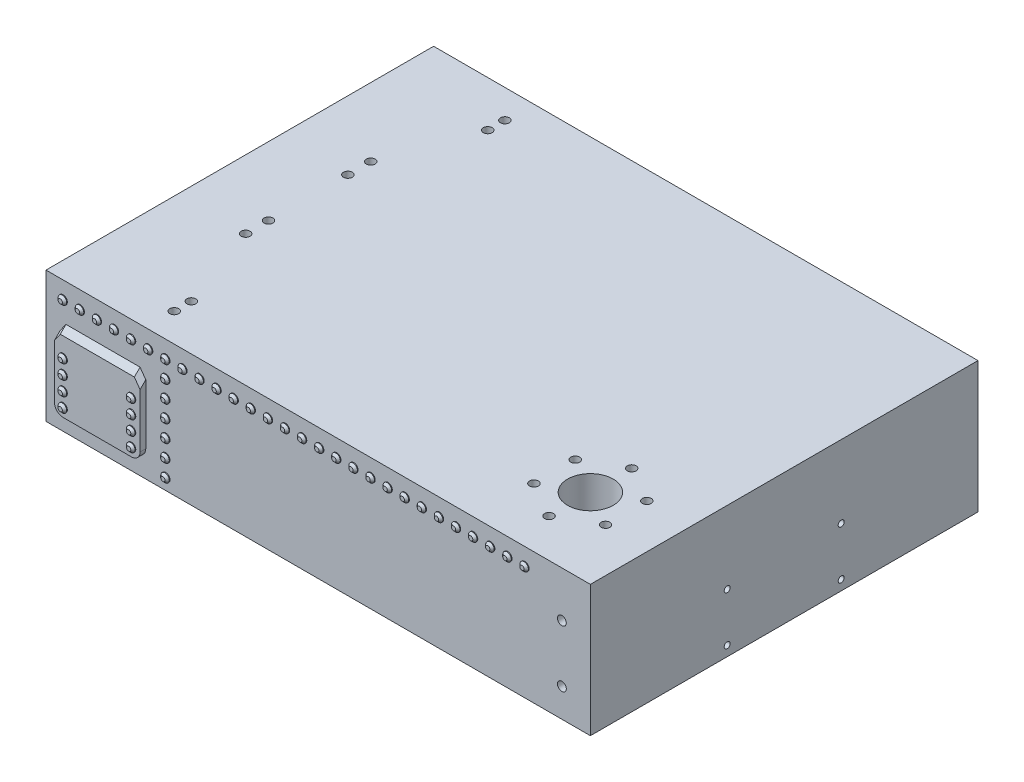
SolidWorks part; units mm, degrees
ref_plane "Front Plane" through (0, 0, 0) normal (0, 0, 1) x (1, 0, 0)
ref_plane "Top Plane" through (0, 0, 0) normal (0, 1, 0) x (1, 0, 0)
ref_plane "Right Plane" through (0, 0, 0) normal (1, 0, 0) x (0, 0, -1)
sketch "Sketch1" plane through (0, 0, 0) normal (0, 1, 0) x (1, 0, 0)
  line L1 (0, 0) -> (191, 0)
  line L2 (0, 0) -> (0, 136)
  line L3 (0, 136) -> (191, 136)
  line L4 (191, 0) -> (191, 136)
  dimension "D1" = 191
  dimension "D2" = 136
extrude "Boss-Extrude1" add sketch "Sketch1" along normal blind 46
sketch "Sketch3" plane through (0, 0, 0) normal (0, -1, 0) x (1, 0, 0)
  line L0 (0, -136) -> (0, 0) construction
  line L1 (5, -5) -> (186, -5)
  line L2 (5, -5) -> (5, -131)
  line L3 (5, -131) -> (186, -131)
  line L4 (186, -5) -> (186, -131)
  line L6 (191, -136) -> (0, -136) construction
  line L7 (191, 0) -> (191, -136) construction
  line L8 (0, 0) -> (191, 0) construction
  dimension "D1" = 5
  dimension "D2" = 5
  dimension "D3" = 5
  dimension "D4" = 5
extrude "Cut-Extrude1" cut sketch "Sketch3" against normal offset from surface (41 mm away) 5 contours L2 L3 L4 L1 up to face at (95.5, 46, -68)
ref_point "FrontLeft"
sketch "Sketch5" plane through (0, 0, -136) normal (0, 0, -1) x (-1, 0, 0)
  line L0 (-191, 46) -> (-119.5, 46)
  line L1 (-191, 46) -> (0, 46) construction
  line L2 (-119.5, 46) -> (-119.5, 0) construction
  line L3 (-191, 0) -> (0, 0) construction
  point P5 (-119.5, 23)
  dimension "D1" = 71.5
sketch "Sketch8" plane through (0, 0, 0) normal (0, 0, 1) x (1, 0, 0)
  line L1 (119.5, 46) -> (119.5, 0) construction
  line L2 (0, 46) -> (191, 46) construction
  line L3 (0, 0) -> (191, 0) construction
  point P0 (119.5, 23)
ref_point "SuspensionMountLeft"
ref_point "SuspensionMountRight"
sketch "Sketch9" plane through (0, 0, -136) normal (0, 0, -1) x (-1, 0, 0)
  line L0 (0, 46) -> (0, 0) construction
  line L1 (-5, 31) -> (-35, 31)
  line L2 (-5, 31) -> (-5, 6.2153)
  line L3 (-5, 6.2153) -> (-35, 6.2153)
  line L4 (-35, 31) -> (-35, 6.2153)
  line L5 (-191, 46) -> (0, 46) construction
  dimension "D1" = 5
  dimension "D2" = 15
  dimension "D3" = 30
extrude "Boss-Extrude2" add sketch "Sketch9" along normal blind 2
chamfer "Chamfer2" distance 2 angle 45 1 edges at (20, 31, -136)
fillet "Fillet1" radius 3 2 edges at (35, 6.2153, -137) (5, 6.2153, -137)
chamfer "Chamfer3" distance 2 angle 45 2 edges at (35, 32, -137) (5, 32, -137)
sketch "Sketch10" plane through (0, 0, 0) normal (0, 0, 1) x (1, 0, 0)
  line L4 (35, 31) -> (5, 31)
  line L5 (35, 6.2153) -> (35, 31)
  line L6 (5, 6.2153) -> (35, 6.2153)
  line L7 (5, 31) -> (5, 6.2153)
  line L8 (35, 31) -> (5, 31)
  line L9 (35, 6.2153) -> (35, 31)
  line L10 (5, 6.2153) -> (35, 6.2153)
  line L11 (5, 31) -> (5, 6.2153)
  dimension "D1" = 0
extrude "Boss-Extrude3" add sketch "Sketch10" along normal blind 2
chamfer "Chamfer4" distance 2 angle 45 1 edges at (20, 31, 0)
fillet "Fillet2" radius 3 2 edges at (35, 6.2153, 1) (5, 6.2153, 1)
chamfer "Chamfer5" distance 2 angle 45 2 edges at (35, 32, 1) (5, 32, 1)
sketch "Sketch23" plane through (0, 0, 2) normal (0, 0, 1) x (1, 0, 0)
  line L0 (8, 9.2153) -> (8, 31) construction
  line L1 (33, 31) -> (7, 31) construction
  line L2 (32, 9.2153) -> (32, 31) construction
  circle A0 centre (8, 9.2153) radius 1.5
  circle A1 centre (32, 9.2153) radius 1.5
  circle A2 centre (8, 14.2153) radius 1.5
  circle A3 centre (32, 14.2153) radius 1.5
  circle A4 centre (8, 19.2153) radius 1.5
  circle A5 centre (32, 19.2153) radius 1.5
  circle A6 centre (8, 24.2153) radius 1.5
  circle A7 centre (32, 24.2153) radius 1.5
  dimension "D1" = 3
  dimension "D2" = 3
  dimension "D3" = 4
extrude "Boss-Extrude8" add sketch "Sketch23" along normal blind 1 contours A4 | A2 | A0 | A1 | A3 | A5 | A7 | A6 region at (8, 9.2153, 2) region at (32, 9.2153, 2) region at (8, 14.2153, 2) region at (32, 14.2153, 2) region at (8, 19.2153, 2) region at (32, 19.2153, 2) region at (32, 24.2153, 2)
chamfer "Chamfer11" distance 0.75 angle 45 8 edges at (9.5, 24.2153, 3) (33.5, 9.2153, 3) (33.5, 14.2153, 3) (33.5, 19.2153, 3) (33.5, 24.2153, 3) (9.5, 9.2153, 3) (9.5, 14.2153, 3) (9.5, 19.2153, 3)
ref_plane "Plane1" through (0, 0, -68) normal (0, 0, 1) x (1, 0, 0)
mirror "Mirror1" about plane through (0, 0, -68) normal (0, 0, 1) of "Chamfer11", "Boss-Extrude8"
sketch "Sketch18" plane through (0, 41, 0) normal (0, -1, 0) x (1, 0, 0)
  line L25 (77.9594, -66) -> (76.1297, -62.8309)
  line L26 (76.1297, -62.8309) -> (72.4703, -62.8309)
  line L27 (72.4703, -62.8309) -> (70.6406, -66)
  line L28 (70.6406, -66) -> (72.4703, -69.1691)
  line L29 (72.4703, -69.1691) -> (76.1297, -69.1691)
  line L30 (76.1297, -69.1691) -> (77.9594, -66)
  line L31 (178.5415, -60.5) -> (176.5207, -57)
  line L32 (176.5207, -57) -> (172.4793, -57)
  line L33 (172.4793, -57) -> (170.4585, -60.5)
  line L34 (170.4585, -60.5) -> (172.4793, -64)
  line L35 (172.4793, -64) -> (176.5207, -64)
  line L36 (176.5207, -64) -> (178.5415, -60.5)
  line L37 (78.3415, -114) -> (76.3207, -110.5)
  line L38 (76.3207, -110.5) -> (72.2793, -110.5)
  line L39 (72.2793, -110.5) -> (70.2585, -114)
  line L40 (70.2585, -114) -> (72.2793, -117.5)
  line L41 (72.2793, -117.5) -> (76.3207, -117.5)
  line L42 (76.3207, -117.5) -> (78.3415, -114)
  line L43 (178.5415, -113) -> (176.5207, -109.5)
  line L44 (176.5207, -109.5) -> (172.4793, -109.5)
  line L45 (172.4793, -109.5) -> (170.4585, -113)
  line L46 (170.4585, -113) -> (172.4793, -116.5)
  line L47 (172.4793, -116.5) -> (176.5207, -116.5)
  line L48 (176.5207, -116.5) -> (178.5415, -113)
  circle A1 centre (74.3, -66) radius 3.1691 construction
  circle A2 centre (174.5, -60.5) radius 1.5
  circle A3 centre (174.5, -60.5) radius 1.5
  circle A4 centre (174.5, -113) radius 1.5
  circle A5 centre (174.5, -113) radius 1.5
  circle A6 centre (74.3, -114) radius 1.5
  circle A7 centre (74.3, -114) radius 1.5
  circle A8 centre (74.3, -66) radius 1.5
  circle A12 centre (74.3, -66) radius 1.5
  circle A13 centre (174.5, -60.5) radius 3.5 construction
  circle A14 centre (74.3, -114) radius 3.5 construction
  circle A15 centre (174.5, -113) radius 3.5 construction
  dimension "D1" = 0
  dimension "D2" = 0
  dimension "D3" = 0
  dimension "D4" = 0
extrude "Boss-Extrude7" add sketch "Sketch18" along normal blind 14 contours L29 L30 L25 L26 L27 L28 A12 | A12 | L41 L42 L37 L38 L39 L40 A7 | A7 | L47 L48 L43 L44 L45 L46 A5 | A5 | L35 L36 L31 L32 L33 L34 A3 | A3 region at (76.9607, 41, -67.5361) region at (177.4385, 41, -62.1965) region at (77.2385, 41, -115.6965) region at (177.4385, 41, -114.6965) region at (174.5, 41, -60.5) region at (174.5, 41, -113) region at (74.3, 41, -114) region at (74.3, 41, -66)
sketch "Sketch22" plane through (0, 0, 0) normal (-1, 0, 0) x (0, 0, 1)
  line L0 (0, 46) -> (0, 0) construction
  line L1 (-10, 10) -> (-80, 10)
  line L2 (-10, 10) -> (-10, 38)
  line L3 (-10, 38) -> (-80, 38)
  line L4 (-80, 10) -> (-80, 38)
  line L5 (-136, 0) -> (0, 0) construction
  line L6 (-136, 46) -> (0, 46) construction
  dimension "D1" = 10
  dimension "D2" = 10
  dimension "D3" = 8
  dimension "D4" = 70
extrude "Cut-Extrude2" [suppressed] cut sketch "Sketch22" against normal up to next
chamfer "Chamfer10" [suppressed] distance 28 angle 45
fillet "Fillet3" [suppressed] radius 3
sketch "Sketch24" plane through (0, 0, 0) normal (0, 0, 1) x (1, 0, 0)
  line L0 (0, 40) -> (191, 40) construction
  line L1 (0, 46) -> (0, 0) construction
  line L2 (191, 46) -> (191, 0) construction
  line L3 (0, 46) -> (191, 46) construction
  circle A0 centre (6, 40) radius 1.5
  circle A1 centre (12, 40) radius 1.5
  circle A2 centre (18, 40) radius 1.5
  circle A3 centre (24, 40) radius 1.5
  circle A4 centre (30, 40) radius 1.5
  circle A5 centre (36, 40) radius 1.5
  circle A6 centre (42, 40) radius 1.5
  circle A7 centre (48, 40) radius 1.5
  circle A8 centre (54, 40) radius 1.5
  circle A9 centre (60, 40) radius 1.5
  circle A10 centre (66, 40) radius 1.5
  circle A11 centre (72, 40) radius 1.5
  circle A12 centre (78, 40) radius 1.5
  circle A13 centre (84, 40) radius 1.5
  circle A14 centre (90, 40) radius 1.5
  circle A15 centre (96, 40) radius 1.5
  circle A16 centre (102, 40) radius 1.5
  circle A17 centre (108, 40) radius 1.5
  circle A18 centre (114, 40) radius 1.5
  circle A19 centre (120, 40) radius 1.5
  circle A20 centre (126, 40) radius 1.5
  circle A21 centre (132, 40) radius 1.5
  circle A22 centre (138, 40) radius 1.5
  circle A23 centre (144, 40) radius 1.5
  circle A24 centre (150, 40) radius 1.5
  circle A25 centre (156, 40) radius 1.5
  circle A26 centre (162, 40) radius 1.5
  circle A27 centre (168, 40) radius 1.5
  circle A28 centre (42, 34) radius 1.5
  circle A29 centre (42, 28) radius 1.5
  circle A30 centre (42, 22) radius 1.5
  circle A31 centre (42, 16) radius 1.5
  circle A32 centre (42, 10) radius 1.5
  circle A33 centre (42, 4) radius 1.5
  dimension "D2" = 3
  dimension "D1" = 6
  dimension "D3" = 6
  dimension "D4" = 28
  dimension "D5" = 7
extrude "Boss-Extrude9" add sketch "Sketch24" along normal blind 1
chamfer "Chamfer12" distance 0.75 angle 45 34 edges at (169.5, 40, 1) (163.5, 40, 1) (157.5, 40, 1) (151.5, 40, 1) (145.5, 40, 1) (139.5, 40, 1) (133.5, 40, 1) (127.5, 40, 1) (121.5, 40, 1) (115.5, 40, 1) (109.5, 40, 1) (103.5, 40, 1) (97.5, 40, 1) (91.5, 40, 1) (85.5, 40, 1) (79.5, 40, 1) (73.5, 40, 1) (67.5, 40, 1) (43.5, 4, 1) (43.5, 10, 1) (43.5, 16, 1) (43.5, 22, 1) (43.5, 28, 1) (43.5, 34, 1) (61.5, 40, 1) (55.5, 40, 1) (49.5, 40, 1) (43.5, 40, 1) (37.5, 40, 1) (31.5, 40, 1) (25.5, 40, 1) (19.5, 40, 1) (13.5, 40, 1) (7.5, 40, 1)
mirror "Mirror3" about plane through (0, 0, -68) normal (0, 0, 1) of "Chamfer12", "Boss-Extrude9"
sketch "Sketch25" plane through (0, 0, -131) normal (0, 0, 1) x (1, 0, 0)
  circle A0 centre (181, 30) radius 1.55 construction
  circle A1 centre (181, 10) radius 1.55 construction
  circle A2 centre (181, 30) radius 1.55
  circle A3 centre (181, 10) radius 1.55
extrude "Cut-Extrude3" cut sketch "Sketch25" against normal through all
sketch "Sketch26" plane through (0, 0, -5) normal (0, 0, -1) x (-1, 0, 0)
  circle A1 centre (-181, 10) radius 1.55
  circle A2 centre (-181, 10) radius 1.55
  circle A3 centre (-181, 30) radius 1.55
  circle A4 centre (-181, 30) radius 1.55
  dimension "D1" = 0
  dimension "D2" = 0
extrude "Cut-Extrude4" cut sketch "Sketch26" against normal through all
sketch "Sketch27" plane through (0, 46, 0) normal (0, 1, 0) x (1, 0, 0)
  line L0 (191, 0) -> (191, 136) construction
  line L1 (0, 0) -> (191, 0) construction
  circle A0 centre (163, 28) radius 1
  dimension "D1" = 2
  dimension "D2" = 28
  dimension "D3" = 28
sketch "Sketch28" plane through (0, 41, 0) normal (0, -1, 0) x (1, 0, 0)
  circle A0 centre (163, -13.5) radius 1.55 construction
  circle A1 centre (163, -28) radius 18
  circle A2 centre (163, -28) radius 18
  circle A3 centre (163, -28) radius 8
  circle A4 centre (163, -28) radius 8
  circle A5 centre (175.5574, -20.75) radius 1.55 construction
  circle A6 centre (175.5574, -35.25) radius 1.55 construction
  circle A7 centre (163, -42.5) radius 1.55 construction
  circle A8 centre (150.4426, -35.25) radius 1.55 construction
  circle A9 centre (150.4426, -20.75) radius 1.55 construction
  circle A10 centre (163, -13.5) radius 1.55
  circle A11 centre (175.5574, -20.75) radius 1.55
  circle A12 centre (175.5574, -35.25) radius 1.55
  circle A13 centre (163, -42.5) radius 1.55
  circle A14 centre (150.4426, -35.25) radius 1.55
  circle A15 centre (150.4426, -20.75) radius 1.55
  circle A17 centre (163, -28) radius 11
  circle A18 centre (163, -28) radius 11
  dimension "D1" = 0
  dimension "D2" = 0
  dimension "D3" = 0
extrude "Cut-Extrude5" cut sketch "Sketch28" against normal through all contours A13 | A12 | A11 | A10 | A15 | A14 region at (163, 41, -13.5) region at (175.5574, 41, -20.75) region at (175.5574, 41, -35.25) region at (163, 41, -42.5) region at (150.4426, 41, -35.25) region at (150.4426, 41, -20.75)
extrude "Cut-Extrude6" cut sketch "Sketch28<3>" against normal through all contours A4 region at (163, 41, -28)
sketch "Sketch28<3>" plane through (0, 41, 0) normal (0, -1, 0) x (1, 0, 0) same geometry as "Sketch28"
extrude "Boss-Extrude10" add sketch "Sketch28<4>" along normal blind 40 contours A18 A4 region at (152.3111, 41, -28)
sketch "Sketch28<4>" plane through (0, 41, 0) normal (0, -1, 0) x (1, 0, 0) same geometry as "Sketch28"
sketch "Sketch29" plane through (0, 1, 0) normal (0, -1, 0) x (1, 0, 0)
  line L0 (163, -28) -> (163, -43.0058) construction
  line L1 (163, -43.0058) -> (162, -43.0058)
  line L2 (163, -43.0058) -> (164, -43.0058)
  line L3 (164, -43.0058) -> (164, -13.0058)
  line L4 (164, -13.0058) -> (162, -13.0058)
  line L5 (162, -13.0058) -> (162, -43.0058)
  dimension "D2" = 1
  dimension "D1" = 1
  dimension "D3" = 30
extrude "Cut-Extrude7" cut sketch "Sketch29" against normal blind 20
ref_plane "Plane2" through (163, 46, -28) normal (0, 0, 1) x (1, 0, 0)
sketch "Sketch30" plane through (163, 46, -28) normal (0, 0, 1) x (1, 0, 0)
  line L0 (11, -5) -> (11, -46) construction
  line L1 (11, -45) -> (11, -5) construction
  line L2 (18, -5) -> (18, -46) construction
  line L3 (18, -5) -> (11, -25.5) construction
  line L4 (23, -5) -> (-158, -5)
  line L5 (-158, -5) -> (-158, -46)
  line L6 (-158, -46) -> (23, -46)
  line L7 (23, -46) -> (23, -5)
  line L8 (23, -5) -> (-158, -5)
  line L9 (-158, -5) -> (-158, -46)
  line L10 (-158, -46) -> (23, -46)
  line L11 (23, -46) -> (23, -5)
  line L12 (17, -7.9286) -> (12, -22.5714)
  line L13 (17, -7.9286) -> (17, -5)
  line L14 (17, -5) -> (17, -4.9)
  line L15 (12, -22.5714) -> (11, -22.5714)
  line L16 (11, -22.5714) -> (10.9, -22.5714)
  line L17 (10.9, -22.5714) -> (10.9, -4.9)
  line L18 (10.9, -4.9) -> (17, -4.9)
  dimension "D2" = 1
  dimension "D3" = 1
  dimension "D4" = 0.1
  dimension "D5" = 0.1
  dimension "D1" = 0
extrude "Boss-Extrude11" add sketch "Sketch30" along normal mid plane 3 contours L17 L16 L15 L12 L13 L8 region at (176.2325, 34.2396, -28)
ref_axis "Axis1" through (163, 46, -28) along (0, -1, 0)
pattern_circular "CirPattern1" count 6 over 360 about axis through (163, 46, -28) along (0, -1, 0) of "Boss-Extrude11"
chamfer "Chamfer13" distance 0.5 angle 45 2 edges at (174, 1, -28) (152, 1, -28)
sketch "Sketch31" plane through (0, 41, 0) normal (0, -1, 0) x (1, 0, 0)
  circle A0 centre (35, -16) radius 1.55 construction
  circle A1 centre (35, -10) radius 1.55 construction
  circle A2 centre (35, -126) radius 1.55 construction
  circle A3 centre (35, -120) radius 1.55 construction
  circle A4 centre (35, -16) radius 1.55
  circle A5 centre (35, -10) radius 1.55
  circle A6 centre (35, -126) radius 1.55
  circle A7 centre (35, -120) radius 1.55
extrude "Cut-Extrude8" cut sketch "Sketch31" against normal up to next
sketch "Sketch32" plane through (5, 0, 0) normal (1, 0, 0) x (0, 0, -1)
  circle A0 centre (125.5, 17.25) radius 1.55 construction
  circle A1 centre (10.5, 17.25) radius 1.55 construction
  circle A2 centre (125.5, 17.25) radius 1.55
  circle A3 centre (10.5, 17.25) radius 1.55
extrude "Cut-Extrude9" cut sketch "Sketch32" against normal up to next
sketch "Sketch35" plane through (0, 41, 0) normal (0, -1, 0) x (1, 0, 0)
  circle A0 centre (24, -46.0692) radius 1.55 construction
  circle A1 centre (24, -54.0692) radius 1.55 construction
  circle A2 centre (24, -81.9308) radius 1.55 construction
  circle A3 centre (24, -89.9308) radius 1.55 construction
  circle A4 centre (24, -46.0692) radius 1.55
  circle A5 centre (24, -54.0692) radius 1.55
  circle A6 centre (24, -81.9308) radius 1.55
  circle A7 centre (24, -89.9308) radius 1.55
extrude "Cut-Extrude11" cut sketch "Sketch35" against normal up to next
sketch "Sketch36" plane through (0, 46, 0) normal (0, 1, 0) x (1, 0, 0)
  line L0 (191, 68) -> (85, 68) construction
  line L1 (191, 0) -> (191, 136) construction
  dimension "D1" = 106
sketch "Sketch37" plane through (0, 0, 0) normal (0, -1, 0) x (1, 0, 0)
  line L4 (0, -136) -> (142.2, -136)
  line L5 (0, 0) -> (0, -136)
  line L6 (142.2, 0) -> (0, 0)
  line L7 (142.2, -136) -> (142.2, 0)
  line L8 (0, -136) -> (142.2, -136)
  line L9 (0, 0) -> (0, -136)
  line L10 (142.2, 0) -> (0, 0)
  line L11 (142.2, -136) -> (142.2, 0)
  arc A0 (8, -131) -> (5, -128) centre (5, -131) ccw construction
  arc A1 (5, -8) -> (8, -5) centre (5, -5) ccw construction
  arc A2 (134.2, -5) -> (137.2, -8) centre (137.2, -5) ccw construction
  arc A3 (137.2, -128) -> (134.2, -131) centre (137.2, -131) ccw construction
  arc A4 (8, -131) -> (5, -128) centre (5, -131) ccw
  arc A5 (5, -8) -> (8, -5) centre (5, -5) ccw
  arc A6 (134.2, -5) -> (137.2, -8) centre (137.2, -5) ccw
  arc A7 (137.2, -128) -> (134.2, -131) centre (137.2, -131) ccw
  circle A8 centre (5, -131) radius 3
  circle A9 centre (5, -5) radius 3
  circle A10 centre (137.2, -5) radius 3
  circle A11 centre (137.2, -131) radius 3
  line M9 (5, -131) -> (5, -5)
  line M10 (5, -5) -> (186, -5)
  line M12 (186, -131) -> (5, -131)
  dimension "D1" = 0
extrude "Boss-Extrude12" add sketch "Sketch37" against normal blind 12 contours A11 A7 M12 | A6 A10 M10 | A5 M9 M10 | A4 M12 M9 region at (137.2, 0, -129.7268) region at (137.2, 0, -6.2732) region at (6.2732, 0, -129.7268) region at (6.2732, 0, -6.2732)
chamfer "Chamfer14" distance 2.999 angle 45 4 edges at (7.1213, 12, -128.8787) (137.2, 12, -128) (137.2, 12, -8) (7.1213, 12, -7.1213)
sketch "Sketch38" plane through (0, 0, 0) normal (0, -1, 0) x (1, 0, 0)
  circle A0 centre (137.2, -131) radius 1.55
  circle A1 centre (137.2, -5) radius 1.55
  circle A2 centre (5, -5) radius 1.55
  circle A3 centre (5, -131) radius 1.55
  dimension "D1" = 3.1
  dimension "D2" = 3.1
  dimension "D3" = 3.1
  dimension "D4" = 3.1
extrude "Cut-Extrude12" cut sketch "Sketch38" against normal blind 2
sketch "Sketch39" plane through (0, 27, 0) normal (0, -1, 0) x (1, 0, 0)
  point P0 (74.3, -66)
  point P1 (74.3, -114)
  point P2 (174.5, -113)
  point P3 (174.5, -60.5)
hole_wizard "Ø2.0mm Dowel Hole1" positions "Sketch41" profile "Sketch42" hole size "Ø2.0" standard "ANSI Metric"
sketch "Sketch41" plane through (0, 27, 0) normal (0, -1, 0) x (-1, 0, 0)
  point P0 (-74.3, 66)
  point P3 (-74.3, 114)
  point P6 (-174.5, 113)
  point P9 (-174.5, 60.5)
sketch "Sketch42" plane through (74.3, 27, -66) normal (1, 0, 0) x (0, 0, -1)
  line L0 (0, 0) -> (0, 12.6009)
  line L1 (0, 12.6009) -> (1, 12)
  line L2 (1, 12) -> (1, 0)
  line L5 (1, 0) -> (0, 0)
  line L10 (0, 12.6009) -> (-1, 12) construction
  line L11 (0, -6.35) -> (0, 107.95) construction
  dimension "Hole Dia." = 2
  dimension "Hole Depth" = 12
  dimension "Drill Angle" = 118
sketch "Sketch43" plane through (5, 0, 0) normal (1, 0, 0) x (0, 0, -1)
  circle A1 centre (48, 15.95) radius 1.05
  circle A2 centre (48, 15.95) radius 1.05
  circle A3 centre (88, 15.95) radius 1.05
  circle A4 centre (88, 15.95) radius 1.05
  circle A5 centre (88, -1.05) radius 1.05
  circle A6 centre (88, -1.05) radius 1.05
  circle A7 centre (48, -1.05) radius 1.05
  circle A8 centre (48, -1.05) radius 1.05
  dimension "D1" = 0
  dimension "D2" = 0
  dimension "D3" = 0
  dimension "D4" = 0
extrude "Cut-Extrude13" cut sketch "Sketch43" against normal through all
sketch "Sketch44" plane through (191, 0, 0) normal (1, 0, 0) x (0, 0, -1)
  circle A1 centre (48, 20.5) radius 1.05
  circle A2 centre (48, 20.5) radius 1.05
  circle A3 centre (88, 20.5) radius 1.05
  circle A4 centre (88, 20.5) radius 1.05
  circle A5 centre (88, 3.5) radius 1.05
  circle A6 centre (88, 3.5) radius 1.05
  circle A7 centre (48, 3.5) radius 1.05
  circle A8 centre (48, 3.5) radius 1.05
  dimension "D1" = 0
  dimension "D2" = 0
  dimension "D3" = 0
  dimension "D4" = 0
extrude "Cut-Extrude14" cut sketch "Sketch44" against normal up to next
